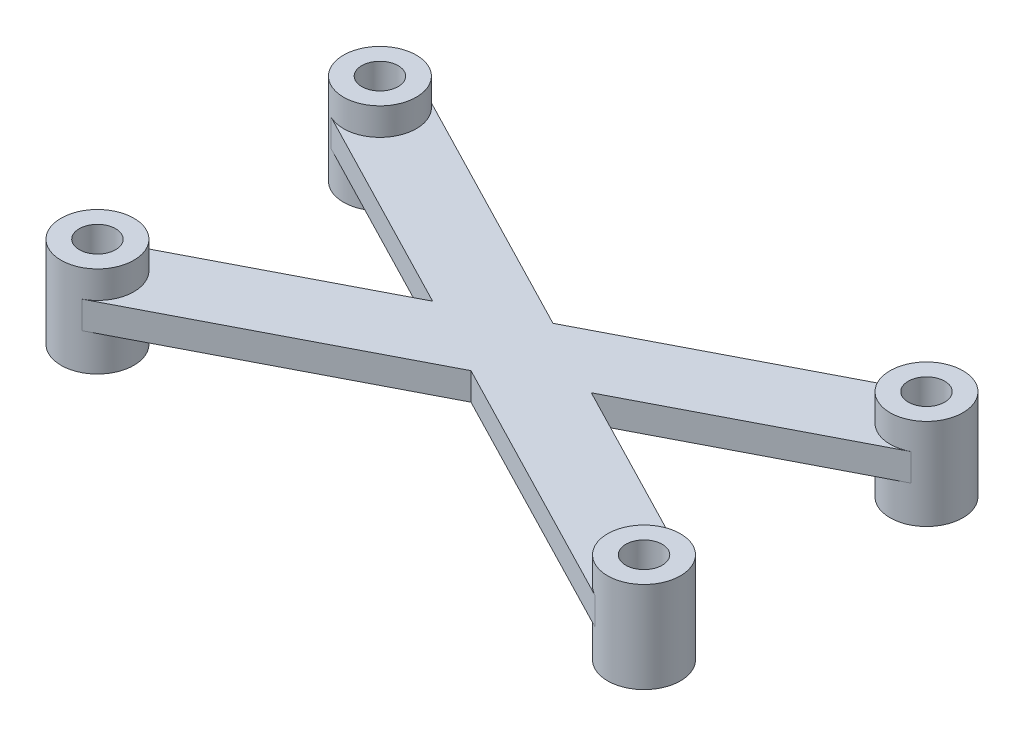
SolidWorks part; units mm, degrees
ref_plane "Alzado" through (0, 0, 0) normal (0, 0, 1) x (1, 0, 0)
ref_plane "Planta" through (0, 0, 0) normal (0, 1, 0) x (1, 0, 0)
ref_plane "Vista lateral" through (0, 0, 0) normal (1, 0, 0) x (0, 0, -1)
sketch "Croquis1" plane through (0, 0, 0) normal (0, 1, 0) x (1, 0, 0)
  line L0 (0, 0) -> (60.02, 0)
  line L1 (60.02, 0) -> (60.02, -31.02)
  line L2 (60.02, -31.02) -> (0, -31.02)
  line L3 (0, 0) -> (60.02, -31.02) construction
  line L4 (60.02, 0) -> (0, -31.02) construction
  circle A0 centre (0, 0) radius 2
  circle A1 centre (0, 0) radius 4
  circle A2 centre (60.02, 0) radius 2
  circle A3 centre (60.02, 0) radius 4
  circle A4 centre (60.02, -31.02) radius 2
  circle A5 centre (60.02, -31.02) radius 4
  circle A6 centre (0, -31.02) radius 2
  circle A7 centre (0, -31.02) radius 4
  circle A8 centre (30.01, -15.51) radius 2
  circle A9 centre (30.01, -15.51) radius 4
  dimension "D1" = 4
  dimension "D2" = 8
  dimension "D5" = 4
  dimension "D6" = 8
  dimension "D7" = 4
  dimension "D8" = 8
  dimension "D9" = 4
  dimension "D10" = 8
  dimension "D11" = 4
  dimension "D12" = 8
  dimension "D3" = 60.02
  dimension "D4" = 31.02
extrude "Saliente-Extruir1" add sketch "Croquis1" along normal blind 4 contours A1 | A0 | A7 | A6 | A3 | A5 | A4 | A2 | A9 | A8
sketch "Croquis3" plane through (0, 4, 0) normal (0, 1, 0) x (1, 0, 0)
  line L0 (30.01, -15.51) -> (22.7508, -15.51)
  line L1 (-1.8365, -3.5535) -> (28.1735, -19.0635)
  line L2 (1.8365, 3.5535) -> (31.8465, -11.9565)
  line L3 (-1.8365, -27.4665) -> (28.1735, -11.9565)
  line L4 (1.8365, -34.5735) -> (31.8465, -19.0635)
  line L5 (30.01, -15.51) -> (30.01, -12.3691)
  line L6 (58.1835, -34.5735) -> (28.1735, -19.0635)
  line L7 (61.8565, -27.4665) -> (31.8465, -11.9565)
  line L8 (61.8565, -3.5535) -> (31.8465, -19.0635)
  line L9 (58.1835, 3.5535) -> (28.1735, -11.9565)
  line L10 (1.8365, 3.5535) -> (30.01, -11.0074)
  line L11 (30.01, -11.0074) -> (58.1835, 3.5535)
  line L12 (61.8565, -3.5535) -> (38.7221, -15.51)
  line L13 (38.7221, -15.51) -> (61.8565, -27.4665)
  line L14 (58.1835, -34.5735) -> (30.01, -20.0126)
  line L15 (30.01, -20.0126) -> (1.8365, -34.5735)
  line L16 (21.2979, -15.51) -> (-1.8365, -3.5535)
  line L17 (-1.8365, -3.5535) -> (21.2979, -15.51)
  line L18 (30.01, -11.0074) -> (28.1735, -11.9565)
  line L19 (30.01, -11.0074) -> (31.8465, -11.9565)
  line L20 (30.01, -20.0126) -> (31.8465, -19.0635)
  line L21 (30.01, -20.0126) -> (28.1735, -19.0635)
  arc A0 (1.8365, 3.5535) -> (-1.8365, -3.5535) centre (0, 0) cw
  arc A1 (-1.8365, -27.4665) -> (1.8365, -34.5735) centre (0, -31.02) cw
  arc A2 (61.8565, -27.4665) -> (58.1835, -34.5735) centre (60.02, -31.02) ccw
  circle A3 centre (0, 0) radius 4 construction
  circle A4 centre (30.01, -15.51) radius 4 construction
  arc A5 (58.1835, 3.5535) -> (61.8565, -3.5535) centre (60.02, 0) ccw
  circle A6 centre (30.01, -15.51) radius 4
  circle A7 centre (30.01, -15.51) radius 2
  arc A8 (1.8365, 3.5535) -> (-1.8365, -3.5535) centre (0, 0) ccw
  circle A9 centre (0, 0) radius 2
  circle A10 centre (0, 0) radius 4
  circle A11 centre (0, -31.02) radius 2
  circle A12 centre (0, -31.02) radius 4
  circle A13 centre (60.02, -31.02) radius 2
  circle A14 centre (60.02, -31.02) radius 4
  circle A15 centre (60.02, 0) radius 2
  circle A16 centre (60.02, 0) radius 4
  arc A17 (-1.8365, -3.5535) -> (1.8365, 3.5535) centre (0, 0) ccw
  arc A18 (28.1735, -11.9565) -> (31.8465, -11.9565) centre (30.01, -15.51) cw
  arc A19 (28.1735, -19.0635) -> (31.8465, -19.0635) centre (30.01, -15.51) ccw
extrude "Saliente-Extruir4" add sketch "Croquis3" along normal blind 3
sketch "Croquis4" plane through (0, 0, 0) normal (0, -1, 0) x (1, 0, 0)
  circle A0 centre (30.01, 15.51) radius 4
  circle A1 centre (30.01, 15.51) radius 2
extrude "Cortar-Extruir1" cut sketch "Croquis4" against normal blind 4
sketch "Croquis5" plane through (0, 4, 0) normal (0, -1, 0) x (1, 0, 0)
  circle A0 centre (30.01, 15.51) radius 2
extrude "Saliente-Extruir5" add sketch "Croquis5" against normal blind 3
sketch "Croquis6" plane through (0, 7, 0) normal (0, 1, 0) x (1, 0, 0)
  circle A0 centre (60.02, 0) radius 2
  circle A1 centre (60.02, 0) radius 4
  circle A2 centre (0, 0) radius 2
  circle A3 centre (0, 0) radius 4
  circle A4 centre (0, -31.02) radius 2
  circle A5 centre (0, -31.02) radius 4
  circle A6 centre (60.02, -31.02) radius 2
  circle A7 centre (60.02, -31.02) radius 4
extrude "Saliente-Extruir6" add sketch "Croquis6" along normal blind 3
